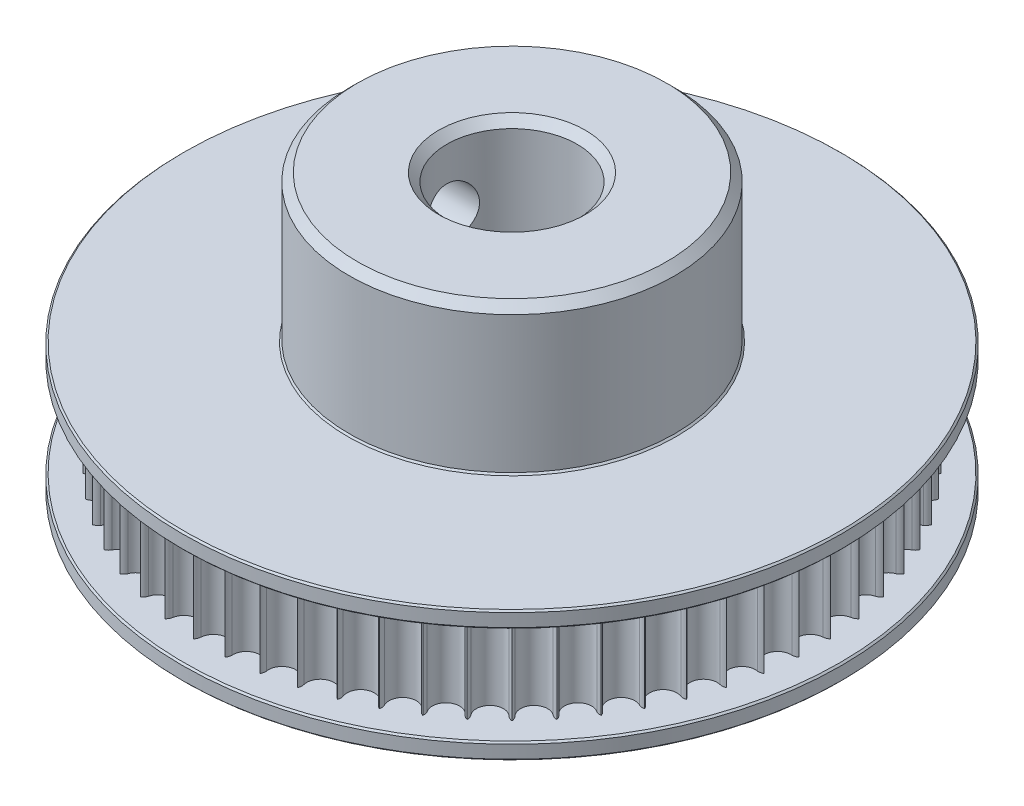
SolidWorks part; units mm, degrees
ref_plane "Front plan" through (0, 0, 0) normal (0, 0, 1) x (1, 0, 0)
ref_plane "Top plan" through (0, 0, 0) normal (0, 1, 0) x (1, 0, 0)
ref_plane "Right plan" through (0, 0, 0) normal (1, 0, 0) x (0, 0, -1)
sketch "Skica2" plane through (0, 0, 0) normal (0, 0, 1) x (1, 0, 0)
  line L0 (10, 9) -> (4, 9)
  line L1 (4, 9) -> (4, -9)
  line L2 (4, -9) -> (5, -9)
  line L3 (0, -9) -> (0, 9) construction
  line L4 (0, 9) -> (4, 9)
  line L5 (0, -9) -> (4, -9)
  line L6 (5, -9) -> (5, -8)
  line L7 (20.25, -1) -> (18.8, -1)
  line L8 (18.8, -1) -> (18.8, -7)
  line L9 (20.25, -1) -> (20.25, 0)
  line L12 (20.25, -8) -> (5, -8)
  line L13 (20.25, 0) -> (10, 0)
  line L14 (20.25, -8) -> (20.25, -7)
  line L15 (18.8, -7) -> (20.25, -7)
  line L16 (10, 0) -> (10, 9)
  point P6 (12.625, -8)
  point P7 (0, 0)
  dimension "D2" = 1
  dimension "D6" = 40.5
  dimension "D3" = 37.6
  dimension "D1" = 8
  dimension "D8" = 18
  dimension "D4" = 1
  dimension "D7" = 20
  dimension "D9" = 9
  dimension "D5" = 1
revolve "Revolute" add sketch "Skica2" angle 360 about L3 region at (10.1468, -1.422, 0)
sketch "Sketch2" plane through (0, -1, 0) normal (0, -1, 0) x (1, 0, 0)
  line L0 (0, 0) -> (0, 18.3305) construction
  line L1 (0, 0) -> (6.3393, 17.699) construction
  line L3 (0, 0) -> (-2.1448, 18.6773) construction
  circle A1 centre (0, 0) radius 17.4945 construction
  circle A2 centre (0, 0) radius 18.3 construction
  arc A3 (-0.8345, 18.281) -> (0.8345, 18.281) centre (0, 18.3305) ccw
  arc A7 (-1.3701, 18.75) -> (-2.1448, 18.6773) centre (0, 0) ccw
  arc A8 (0, 20.2554) -> (2.1448, 18.6773) centre (0.5756, 18.7912) cw
  circle A9 centre (0, 0) radius 18.8 construction
  arc A10 (1.3701, 18.75) -> (2.1448, 18.6773) centre (0, 0) cw
  arc A11 (1.3701, 18.75) -> (0.8345, 18.281) centre (1.3336, 18.2513) ccw
  arc A12 (0, 20.2554) -> (-2.1448, 18.6773) centre (-0.5756, 18.7912) ccw
  arc A13 (-1.3701, 18.75) -> (-0.8345, 18.281) centre (-1.3336, 18.2513) cw
  dimension "D2" = 1
  dimension "D4" = 0.836
  dimension "D6" = 37.6
  dimension "D3" = 1.5733
  dimension "D1" = 0.5
extrude "Cut-Extrude3" cut sketch "Sketch2" along normal up to surface (6 mm away) up to face at (20.25, -7, 0)
pattern_circular "CirPattern1" count 60 over 360 about axis through (0, -9, 0) along (0, -1, 0) of "Cut-Extrude3"
sketch "Sketch3" plane through (0, 0, 0) normal (1, 0, 0) x (0, 0, -1)
  line L0 (0, 9) -> (0, 0.5) construction
  line L1 (4, 9) -> (-4, 9) construction
  circle A0 centre (0, 4.75) radius 1.65
  dimension "D1" = 3.3
extrude "Cut-Extrude2" cut sketch "Sketch3" against normal up to next
chamfer "Chamfer1" distance 1 angle 45 1 edges at (5, -8, 0)
chamfer "Chamfer2" distance 0.5 angle 45 2 edges at (10, 9, 0) (4, 9, 0)
chamfer "Chamfer3" distance 0.1 angle 45 5 edges at (20.25, -8, 0) (20.25, -7, 0) (20.25, -1, 0) (20.25, 0, 0) (10, 0, 0)
sketch "Sketch4" plane through (0, 9, 0) normal (0, 1, 0) x (1, 0, 0)
  line L0 (21.1023, 0) -> (-21.1023, 0) construction
  point P7 (0, 0)
equation "\"`\"=2"
equation "\"D6@Sketch2\"= \"D3@Skica2\""
